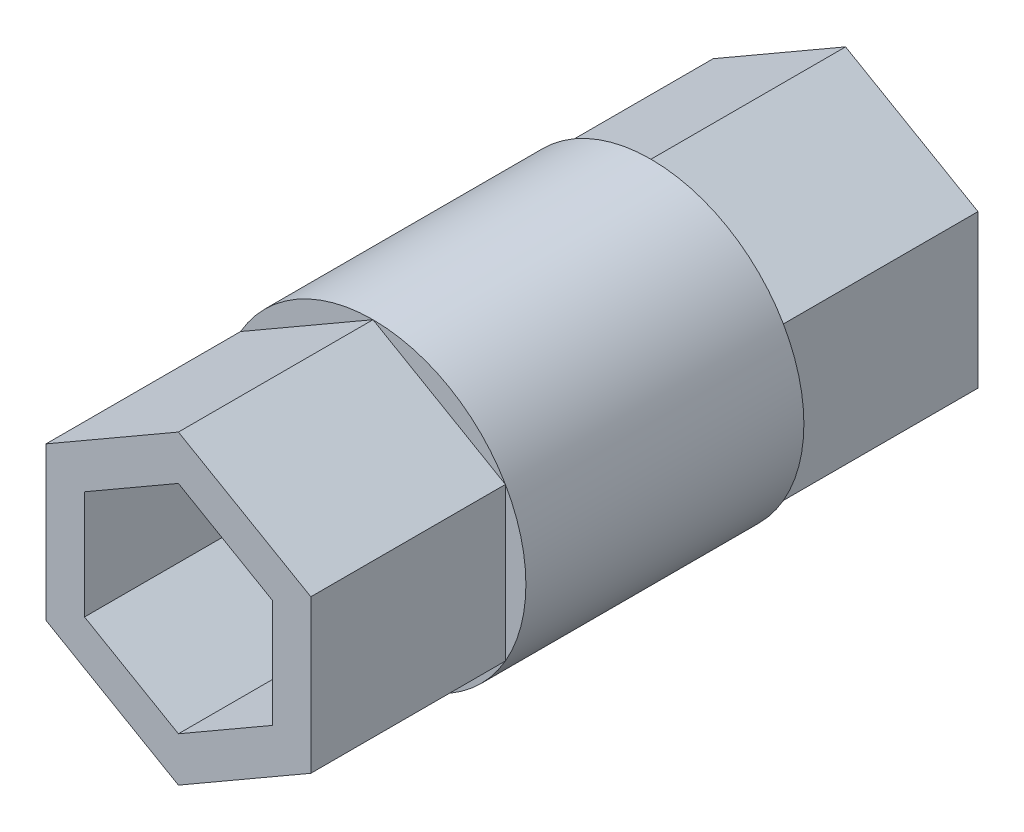
SolidWorks part; units mm, degrees
ref_plane "Front Plane" through (0, 0, 0) normal (0, 0, 1) x (1, 0, 0)
ref_plane "Top Plane" through (0, 0, 0) normal (0, 1, 0) x (1, 0, 0)
ref_plane "Right Plane" through (0, 0, 0) normal (1, 0, 0) x (0, 0, -1)
sketch "Sketch1" plane through (0, 0, 0) normal (0, 0, 1) x (1, 0, 0)
  line L1 (0, -11) -> (9.5263, -5.5)
  line L2 (9.5263, -5.5) -> (9.5263, 5.5)
  line L3 (9.5263, 5.5) -> (0, 11)
  line L4 (0, 11) -> (-9.5263, 5.5)
  line L5 (-9.5263, 5.5) -> (-9.5263, -5.5)
  line L6 (-9.5263, -5.5) -> (0, -11)
  circle A0 centre (0, 0) radius 11
  circle A1 centre (0, 0) radius 9.5263 construction
  circle A2 centre (0, 0) radius 6.4
  dimension "D1" = 22
  dimension "D2" = 12.8
extrude "Boss-Extrude1" add sketch "Sketch1" along normal mid plane 20 contours L4 A0 | L5 A0 | L5 L6 L1 L2 L3 L4 | L3 A0 | L2 A0 | L1 A0 | L6 A0 region at (-4.6176, -7.998, 0) region at (-5.0596, -8.7636, 0) region at (5.0596, -8.7636, 0) region at (10.1193, 0, 0) region at (-10.1193, 0, 0) region at (5.0596, 8.7636, 0) region at (-5.0596, 8.7636, 0)
extrude "Boss-Extrude2" add sketch "Sketch1<3>" along normal mid plane 48 contours L5 L6 L1 L2 L3 L4 A2 | A2 region at (-4.6176, -7.998, 0)
sketch "Sketch1<3>" plane through (0, 0, 0) normal (0, 0, 1) x (1, 0, 0) same geometry as "Sketch1"
sketch "Sketch2" plane through (0, 0, 24) normal (0, 0, 1) x (1, 0, 0)
  line L1 (0, -7.8) -> (6.755, -3.9)
  line L2 (6.755, -3.9) -> (6.755, 3.9)
  line L3 (6.755, 3.9) -> (0, 7.8)
  line L4 (0, 7.8) -> (-6.755, 3.9)
  line L5 (-6.755, 3.9) -> (-6.755, -3.9)
  line L6 (-6.755, -3.9) -> (0, -7.8)
  circle A0 centre (0, 0) radius 6.755 construction
  dimension "D1" = 15.6
extrude "Cut-Extrude3" cut sketch "Sketch2" against normal through all
